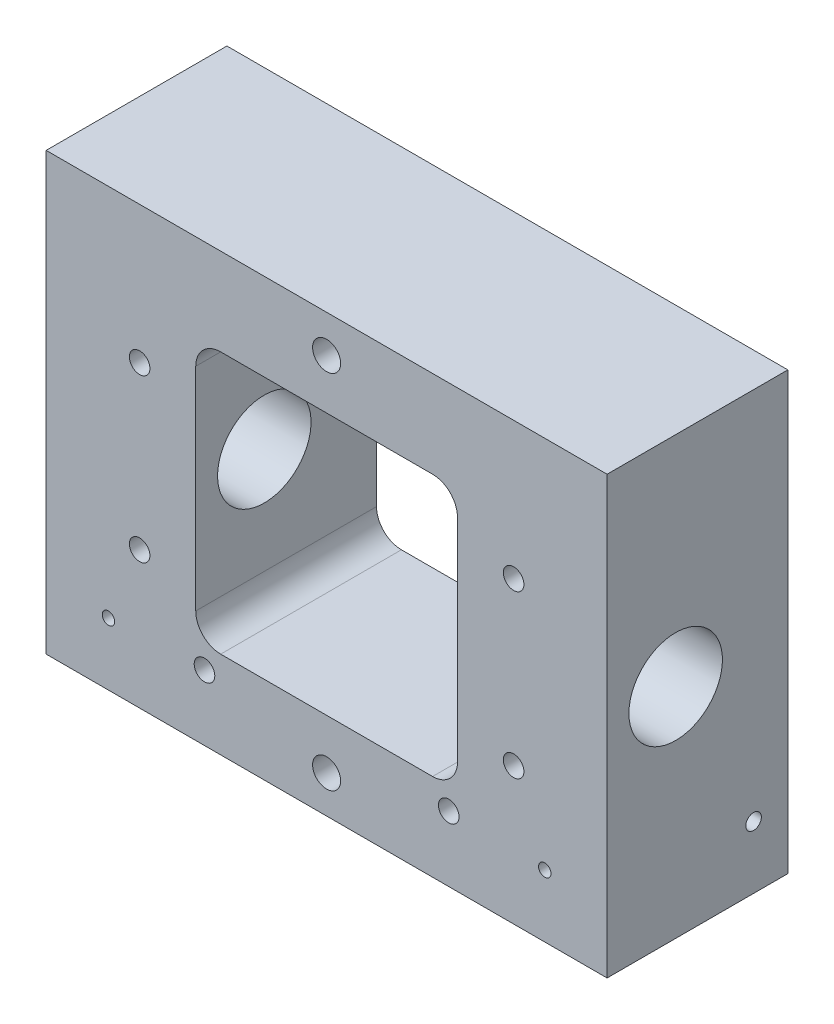
SolidWorks part; units mm, degrees
material "Lega 6061"
ref_plane "Piano frontale" through (0, 0, 0) normal (0, 0, 1) x (1, 0, 0)
ref_plane "Piano superiore" through (0, 0, 0) normal (0, 1, 0) x (1, 0, 0)
ref_plane "Piano destro" through (0, 0, 0) normal (1, 0, 0) x (0, 0, -1)
sketch "Schizzo1" plane through (0, 0, 0) normal (0, 0, 1) x (1, 0, 0)
  line L1 (0, 0) -> (90, 0)
  line L2 (0, 0) -> (0, 70)
  line L3 (0, 70) -> (90, 70)
  line L4 (90, 0) -> (90, 70)
  dimension "D1" = 90
  dimension "D2" = 70
extrude "Estrusione-Estrusione1" add sketch "Schizzo1" against normal blind 29
sketch "Schizzo2" plane through (0, 0, 0) normal (-1, 0, 0) x (0, 0, 1)
  line L0 (-29, 35) -> (0, 35) construction
  line L1 (-29, 70) -> (-29, 0) construction
  line L2 (0, 70) -> (0, 0) construction
  circle A0 centre (-11, 35) radius 7.5
  dimension "D1" = 15
  dimension "D2" = 18
extrude "Taglio-Estrusione1" cut sketch "Schizzo2" against normal through all
sketch "Schizzo3" plane through (0, 0, -29) normal (0, 0, -1) x (-1, 0, 0)
  line L0 (-94.314, 64) -> (4.9562, 64) construction
  line L2 (-90, 70) -> (0, 70) construction
  line L4 (-90, 35) -> (0, 35) construction
  line L5 (-90, 0) -> (-90, 70) construction
  line L6 (0, 70) -> (0, 0) construction
  line L7 (-94.314, 6) -> (4.9562, 6) construction
  line L8 (-45, 70) -> (-45, 0) construction
  line L9 (0, 0) -> (-90, 0) construction
  point P16 (-45, 64)
  point P17 (-45, 6)
  dimension "D1" = 6
hole_wizard "Foro lamato per Vite M4 a testa cilindrica piana-1" positions "Schizzo3D1" profile "Schizzo4" counterbore size "M4" standard "ISO" end condition through all
sketch3d "Schizzo3D1"
  point P0 (45, 64, -29)
  point P3 (45, 6, -29)
sketch "Schizzo4" plane through (45, 64, -29) normal (1, 0, 0) x (0, 1, 0)
  line L0 (0, 0) -> (0, 29)
  line L1 (0, 29) -> (2.25, 29)
  line L3 (2.25, 29) -> (2.25, 2.6)
  line L4 (2.25, 2.6) -> (4, 2.6)
  line L5 (4, 2.6) -> (4, 0)
  line L7 (4, 0) -> (0, 0)
  line L11 (0, -6.35) -> (0, 107.95) construction
  dimension "Thru Hole Dia." = 4.5
  dimension "Thru Hole Depth" = 29
  dimension "C'Bore Dia." = 8
  dimension "C'Bore Depth" = 2.6
ref_axis "Assi1" through (90, 35, -11) along (-1, 0, 0)
sketch "Schizzo14" plane through (0, 0, 0) normal (0, 0, 1) x (1, 0, 0)
  line L0 (45, 70) -> (45, 0) construction
  line L2 (62, 14) -> (28, 14)
  line L3 (66, 18) -> (66, 52)
  line L4 (90, 35) -> (0, 35) construction
  line L5 (62, 56) -> (28, 56)
  line L6 (24, 18) -> (24, 52)
  line L7 (66, 14) -> (24, 56) construction
  line L8 (66, 56) -> (24, 14) construction
  line L9 (0, 0) -> (90, 0) construction
  arc A0 (62, 56) -> (66, 52) centre (62, 52) cw
  arc A1 (66, 18) -> (62, 14) centre (62, 18) cw
  arc A2 (28, 14) -> (24, 18) centre (28, 18) cw
  arc A3 (24, 52) -> (28, 56) centre (28, 52) cw
  point P2 (45, 35)
  point P3 (45, 35)
  dimension "D1" = 4
  dimension "D2" = 42
  dimension "D3" = 42
  dimension "D4" = 14
extrude "Taglio-Estrusione4" cut sketch "Schizzo14" against normal through all
sketch "Schizzo16" plane through (0, 0, 0) normal (0, 0, 1) x (1, 0, 0)
  line L0 (45, 70) -> (45, 0) construction
  line L1 (0, 35) -> (90, 35) construction
  line L2 (0, 70) -> (0, 0) construction
  line L3 (0, 0) -> (90, 0) construction
  circle A0 centre (10, 10) radius 1
  circle A1 centre (80, 10) radius 1
  dimension "D1" = 2
  dimension "D2" = 10
  dimension "D3" = 10
  dimension "D4" = 35
  dimension "D5" = 25
extrude "Taglio-Estrusione6" cut sketch "Schizzo16" against normal through all
sketch "Schizzo17" plane through (0, 0, -29) normal (0, 0, -1) x (-1, 0, 0)
  line L0 (-45, 70) -> (-45, 0.5122) construction
  line L1 (-90, 70) -> (0, 70) construction
  line L2 (-45, 70) -> (-45, 0) construction
  line L3 (0, 35) -> (-90, 35) construction
  circle A0 centre (-10, 10) radius 8
  circle A1 centre (-80, 10) radius 8
  dimension "D1" = 16
extrude "Taglio-Estrusione8" cut sketch "Schizzo17" against normal blind 13
sketch "Schizzo18" plane through (0, 0, 0) normal (0, 0, 1) x (1, 0, 0)
  line L0 (0, 70) -> (90, 0) construction
  line L1 (90, 70) -> (0, 0) construction
  line L2 (45, 35) -> (45, 70) construction
  line L3 (15, 35.0996) -> (15, 74.2174) construction
  line L4 (24, 35) -> (0, 35) construction
  line L5 (24, 52) -> (24, 18) construction
  line L6 (90, 35) -> (0, 35) construction
  line L7 (90, 70) -> (0, 70) construction
  line L8 (45, 70) -> (45, 0) construction
  point P9 (15, 22)
  point P11 (45, 35)
  point P17 (15, 48)
  point P24 (75, 22)
  point P25 (75, 48)
  dimension "D1" = 13
  dimension "D2" = 30
hole_wizard "Foro filettato M4-1" positions "Schizzo20" profile "Schizzo19" tap size "M4" standard "ISO" end condition through all
sketch "Schizzo20" plane through (0, 0, 0) normal (0, 0, 1) x (1, 0, 0)
  point P0 (15, 48)
  point P3 (15, 22)
  point P6 (75, 48)
  point P9 (75, 22)
cosmetic thread "Filettatura del foro1" parameters "D2"=4
cosmetic thread "Filettatura del foro2" parameters "D2"=4
cosmetic thread "Filettatura del foro3" parameters "D2"=4
cosmetic thread "Filettatura del foro4" parameters "D2"=4
sketch "Schizzo19" plane through (15, 48, 0) normal (1, 0, 0) x (0, -1, 0)
  line L0 (0, 0) -> (0, 29)
  line L1 (0, 29) -> (1.65, 29)
  line L2 (1.65, 29) -> (1.65, 0)
  line L5 (1.65, 0) -> (0, 0)
  line L11 (0, -6.35) -> (0, 107.95) construction
  dimension "Thru Tap Drill Dia." = 3.3
  dimension "Thru Tap Drill Depth" = 29
sketch "Schizzo21" plane through (0, 0, -29) normal (0, 0, -1) x (-1, 0, 0)
  line L0 (-70, 73.919) -> (-70, -6.106) construction
  line L1 (-45, 70) -> (-45, 0) construction
  line L2 (-90, 70) -> (0, 0) construction
  line L3 (0, 70) -> (-90, 0) construction
  line L5 (-20, 72.5272) -> (-20, -6.106) construction
  point P6 (-70, 54.4444)
  point P9 (-70, 15.5556)
  point P14 (-20, 54.4444)
  point P15 (-20, 15.5556)
  dimension "D1" = 25
  dimension "D2" = 25
hole_wizard "Foro filettato M3-1" positions "Schizzo23" profile "Schizzo22" tap size "M3" standard "ISO"
sketch "Schizzo23" plane through (0, 0, -29) normal (0, 0, -1) x (-1, 0, 0)
  point P0 (-70, 54.4444)
  point P3 (-70, 15.5556)
  point P6 (-20, 54.4444)
  point P9 (-20, 15.5556)
sketch "Schizzo22" plane through (70, 54.4444, -29) normal (1, 0, 0) x (0, 1, 0)
  line L0 (0, 0) -> (0, 12.7511)
  line L1 (0, 12.7511) -> (1.25, 12)
  line L2 (1.25, 12) -> (1.25, 0)
  line L5 (1.25, 0) -> (0, 0)
  line L10 (0, 12.7511) -> (-1.25, 12) construction
  line L11 (0, -6.35) -> (0, 107.95) construction
  dimension "Tap Drill Dia." = 2.5
  dimension "Tap Drill Depth" = 12
  dimension "Drill Angle" = 118
cosmetic thread "Filettatura del foro5" parameters "D1"=8, "D2"=3
cosmetic thread "Filettatura del foro6" parameters "D1"=8, "D2"=3
cosmetic thread "Filettatura del foro7" parameters "D1"=8, "D2"=3
cosmetic thread "Filettatura del foro8" parameters "D1"=8, "D2"=3
sketch "Schizzo24" plane through (0, 0, 0) normal (-1, 0, 0) x (0, 0, 1)
  line L0 (-16, 18) -> (-16, 2) construction
  line L1 (-16, 10) -> (-29, 10) construction
  point P6 (-23.5, 10)
  dimension "D1" = 7.5
hole_wizard "Foro filettato M3-2" positions "Schizzo26" profile "Schizzo27" tap size "M3" standard "ISO" end condition up to next
sketch "Schizzo26" plane through (0, 0, 0) normal (-1, 0, 0) x (0, 0, 1)
  point P0 (-23.5, 10)
sketch "Schizzo27" plane through (0, 10, -23.5) normal (0, 1, 0) x (0, 0, 1)
  line L0 (0, 0) -> (0, 2)
  line L1 (0, 2) -> (1.25, 2)
  line L2 (1.25, 2) -> (1.25, 0)
  line L5 (1.25, 0) -> (0, 0)
  line L11 (0, -6.35) -> (0, 107.95) construction
  dimension "Thru Tap Drill Dia." = 2.5
  dimension "Thru Tap Drill Depth" = 2
cosmetic thread "Filettatura del foro9" parameters "D2"=3
sketch "Schizzo28" plane through (0, 0, 0) normal (0, -1, 0) x (1, 0, 0)
  line L0 (2, -16) -> (18, -16) construction
  line L1 (10, -16) -> (10, -29) construction
  line L2 (94.314, -29) -> (-4.9562, -29) construction
  point P8 (10, -23.5)
  dimension "D1" = 7.5
hole_wizard "Foro filettato M3-3" positions "Schizzo30" profile "Schizzo31" tap size "M3" standard "ISO" end condition up to next
sketch "Schizzo30" plane through (0, 0, 0) normal (0, -1, 0) x (-1, 0, 0)
  point P0 (-10, 23.5)
sketch "Schizzo31" plane through (10, 0, -23.5) normal (1, 0, 0) x (0, 0, -1)
  line L0 (0, 0) -> (0, 2)
  line L1 (0, 2) -> (1.25, 2)
  line L2 (1.25, 2) -> (1.25, 0)
  line L5 (1.25, 0) -> (0, 0)
  line L11 (0, -6.35) -> (0, 107.95) construction
  dimension "Thru Tap Drill Dia." = 2.5
  dimension "Thru Tap Drill Depth" = 2
cosmetic thread "Filettatura del foro10" parameters "D2"=3
sketch "Schizzo32" plane through (0, 0, 0) normal (0, -1, 0) x (1, 0, 0)
  line L0 (72, -16) -> (88, -16) construction
  line L1 (72, -16) -> (88, -16) construction
  line L2 (80, -16) -> (80, -29) construction
  line L3 (94.314, -29) -> (-4.9562, -29) construction
  line L5 (90, -29) -> (90, 0) construction
  point P9 (80, -23.5)
  dimension "D1" = 7.5
  dimension "D2" = 5.5
  dimension "D3" = 10
hole_wizard "Foro filettato M3-4" positions "Schizzo34" profile "Schizzo35" tap size "M3" standard "ISO" end condition up to next
sketch "Schizzo34" plane through (0, 0, 0) normal (0, -1, 0) x (-1, 0, 0)
  point P0 (-80, 23.5)
sketch "Schizzo35" plane through (80, 0, -23.5) normal (1, 0, 0) x (0, 0, -1)
  line L0 (0, 0) -> (0, 2)
  line L1 (0, 2) -> (1.25, 2)
  line L2 (1.25, 2) -> (1.25, 0)
  line L5 (1.25, 0) -> (0, 0)
  line L11 (0, -6.35) -> (0, 107.95) construction
  dimension "Thru Tap Drill Dia." = 2.5
  dimension "Thru Tap Drill Depth" = 2
cosmetic thread "Filettatura del foro11" parameters "D2"=3
sketch "Schizzo36" plane through (90, 0, 0) normal (1, 0, 0) x (0, 0, -1)
  line L0 (16, 18) -> (16, 2) construction
  line L1 (16, 10) -> (29, 10) construction
  point P8 (23.5, 10)
hole_wizard "Foro filettato M3-5" positions "Schizzo38" profile "Schizzo37" tap size "M3" standard "ISO" end condition up to next
sketch "Schizzo38" plane through (90, 0, 0) normal (1, 0, 0) x (0, 0, -1)
  point P0 (23.5, 10)
cosmetic thread "Filettatura del foro12" parameters "D2"=3
sketch "Schizzo37" plane through (90, 10, -23.5) normal (0, 1, 0) x (0, 0, -1)
  line L0 (0, 0) -> (0, 2)
  line L1 (0, 2) -> (1.25, 2)
  line L2 (1.25, 2) -> (1.25, 0)
  line L5 (1.25, 0) -> (0, 0)
  line L11 (0, -6.35) -> (0, 107.95) construction
  dimension "Thru Tap Drill Dia." = 2.5
  dimension "Thru Tap Drill Depth" = 2
sketch "Schizzo39" plane through (0, 0, 0) normal (0, 0, 1) x (1, 0, 0)
  line L0 (45, 0) -> (45, 37.4704) construction
  point P0 (64.5937, 10.5)
  point P3 (25.4063, 10.5)
hole_wizard "Foro filettato M4-2" positions "Schizzo41" profile "Schizzo40" tap size "M4" standard "ISO"
sketch "Schizzo41" plane through (0, 0, 0) normal (0, 0, 1) x (1, 0, 0)
  point P0 (64.5937, 10.5)
  point P3 (25.4063, 10.5)
sketch "Schizzo40" plane through (64.5937, 10.5, 0) normal (1, 0, 0) x (0, -1, 0)
  line L0 (0, 0) -> (0, 11.0914)
  line L1 (0, 11.0914) -> (1.65, 10.1)
  line L2 (1.65, 10.1) -> (1.65, 0)
  line L5 (1.65, 0) -> (0, 0)
  line L10 (0, 11.0914) -> (-1.65, 10.1) construction
  line L11 (0, -6.35) -> (0, 107.95) construction
  dimension "Tap Drill Dia." = 3.3
  dimension "Tap Drill Depth" = 10.1
  dimension "Drill Angle" = 118
cosmetic thread "Filettatura del foro13" parameters "D1"=8, "D2"=4
cosmetic thread "Filettatura del foro14" parameters "D1"=8, "D2"=4
